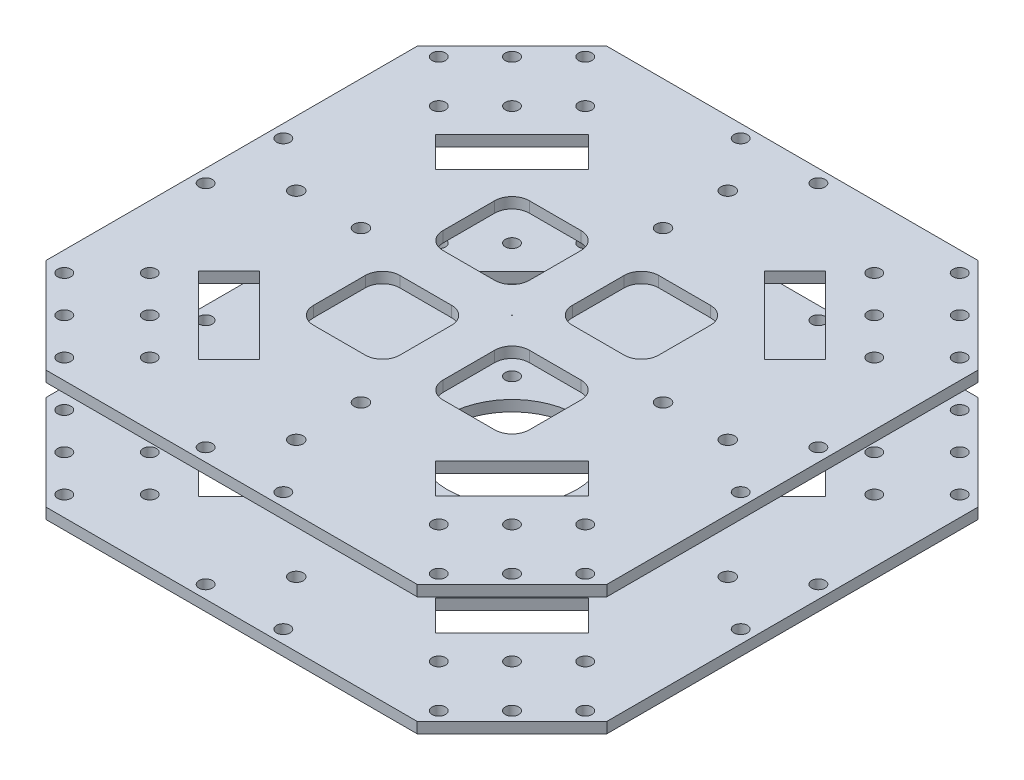
SolidWorks part; units mm, degrees
ref_plane "前视基准面" through (0, 0, 0) normal (0, 0, 1) x (1, 0, 0)
ref_plane "上视基准面" through (0, 0, 0) normal (0, 1, 0) x (1, 0, 0)
ref_plane "右视基准面" through (0, 0, 0) normal (1, 0, 0) x (0, 0, -1)
sketch "草图1" plane through (0, 0, 0) normal (0, 1, 0) x (1, 0, 0)
  line L1 (65, -65) -> (-65, -65)
  line L2 (65, -65) -> (65, 65)
  line L3 (65, 65) -> (-65, 65)
  line L4 (-65, -65) -> (-65, 65)
  line L5 (65, -65) -> (-65, 65) construction
  line L6 (65, 65) -> (-65, -65) construction
  point P0 (0, 0)
  dimension "D1" = 130
  dimension "D2" = 130
extrude "凸台-拉伸1" add sketch "草图1" along normal blind 2.5
ref_plane "基准面4" through (0, 27.5, 0) normal (0, 1, 0) x (1, 0, 0)
sketch "草图2" plane through (0, 27.5, 0) normal (0, 1, 0) x (1, 0, 0)
  line L1 (65, -65) -> (-65, -65)
  line L2 (65, -65) -> (65, 65)
  line L3 (65, 65) -> (-65, 65)
  line L4 (-65, -65) -> (-65, 65)
  line L5 (65, -65) -> (-65, 65) construction
  line L6 (65, 65) -> (-65, -65) construction
  point P0 (0, 0)
  dimension "D1" = 130
  dimension "D2" = 130
extrude "凸台-拉伸2" add sketch "草图2" along normal blind 2.5 separate body
sketch "草图3" plane through (0, 0, 0) normal (0, 1, 0) x (1, 0, 0)
  line L0 (0, 34.0658) -> (0, 0) construction
  line L1 (0, 0) -> (52.3615, 0) construction
  line L2 (-43, 65) -> (-65, 43)
  line L3 (65, 65) -> (-65, 65) construction
  line L4 (-65, 65) -> (-65, -65) construction
  line L5 (-65, 43) -> (-65, 65)
  line L6 (-65, 65) -> (-43, 65)
  line L7 (65, 65) -> (43, 65)
  line L8 (65, 43) -> (65, 65)
  line L9 (43, 65) -> (65, 43)
  line L10 (43, -65) -> (65, -43)
  line L11 (65, -43) -> (65, -65)
  line L12 (65, -65) -> (43, -65)
  line L13 (-65, -65) -> (-43, -65)
  line L14 (-65, -43) -> (-65, -65)
  line L15 (-43, -65) -> (-65, -43)
  dimension "D1" = 22
extrude "切除-拉伸1" cut sketch "草图3" against normal mid plane 500
sketch "草图5" plane through (0, 30, 0) normal (0, 1, 0) x (1, 0, 0)
  line L0 (0, 0) -> (-54, 54) construction
  line L1 (-65, 43) -> (-43, 65) construction
  line L2 (0, 0) -> (0, 31.4738) construction
  line L3 (0, 0) -> (-32.2224, 0) construction
  line L4 (-38.7284, 55.1295) -> (-46.9289, 46.9289) construction
  line L5 (-43.3934, 60.364) -> (-60.364, 43.3934) construction
  circle A2 centre (-60.364, 43.3934) radius 1.55
  circle A3 centre (-43.3934, 60.364) radius 1.55
  circle A4 centre (43.3934, 60.364) radius 1.55
  circle A5 centre (60.364, 43.3934) radius 1.55
  circle A6 centre (60.364, -43.3934) radius 1.55
  circle A7 centre (43.3934, -60.364) radius 1.55
  circle A8 centre (-43.3934, -60.364) radius 1.55
  circle A9 centre (-60.364, -43.3934) radius 1.55
  circle A10 centre (-50.4645, 33.4939) radius 1.55
  circle A11 centre (-33.4939, 50.4645) radius 1.55
  circle A12 centre (33.4939, 50.4645) radius 1.55
  circle A13 centre (50.4645, 33.4939) radius 1.55
  circle A14 centre (33.4939, -50.4645) radius 1.55
  circle A15 centre (50.4645, -33.4939) radius 1.55
  circle A16 centre (-33.4939, -50.4645) radius 1.55
  circle A17 centre (-50.4645, -33.4939) radius 1.55
  circle A18 centre (-51.8787, 51.8787) radius 1.55
  circle A19 centre (-41.9792, 41.9792) radius 1.55
  circle A20 centre (41.9792, 41.9792) radius 1.55
  circle A21 centre (51.8787, 51.8787) radius 1.55
  circle A22 centre (51.8787, -51.8787) radius 1.55
  circle A23 centre (41.9792, -41.9792) radius 1.55
  circle A24 centre (-41.9792, -41.9792) radius 1.55
  circle A25 centre (-51.8787, -51.8787) radius 1.55
  dimension "D1" = 3.1
  dimension "D2" = 3
  dimension "D3" = 24
  dimension "D4" = 7
extrude "切除-拉伸3" cut sketch "草图5" against normal mid plane 500
sketch "草图6" plane through (0, 30, 0) normal (0, 1, 0) x (1, 0, 0)
  circle A0 centre (0, 0) radius 0.05
  dimension "D1" = 0.1
extrude "切除-拉伸4" cut sketch "草图6" against normal blind 10
sketch "草图7" plane through (0, 30, 0) normal (0, 1, 0) x (1, 0, 0)
  line L0 (0, 0) -> (-65, 0) construction
  line L1 (-65, 43) -> (-65, -43) construction
  line L2 (-62, 0) -> (-62, 9) construction
  line L3 (0, 18.3729) -> (0, 0) construction
  line L4 (0, 0) -> (-41.9792, 41.9792) construction
  line L5 (62, 0) -> (62, 9) construction
  line L6 (0, -62) -> (-9, -62) construction
  line L7 (0, 62) -> (-9, 62) construction
  circle A0 centre (-62, 9) radius 1.55
  circle A1 centre (-62, -9) radius 1.55
  circle A2 centre (62, -9) radius 1.55
  circle A3 centre (62, 9) radius 1.55
  circle A4 centre (-9, -62) radius 1.55
  circle A5 centre (9, -62) radius 1.55
  circle A6 centre (9, 62) radius 1.55
  circle A7 centre (-9, 62) radius 1.55
  dimension "D1" = 3.1
  dimension "D2" = 3
  dimension "D3" = 18
extrude "切除-拉伸5" cut sketch "草图7" against normal blind 50
sketch "草图8" plane through (0, 30, 0) normal (0, 1, 0) x (1, 0, 0)
  line L0 (0, 25) -> (0, -25) construction
  line L1 (25, -25) -> (-25, -25)
  line L2 (25, -25) -> (25, 25)
  line L3 (25, 25) -> (-25, 25)
  line L4 (-25, -25) -> (-25, 25)
  line L5 (25, -25) -> (-25, 25) construction
  line L6 (25, 25) -> (-25, -25) construction
  line L7 (-25, 0) -> (25, 0) construction
  line L8 (-5, 25) -> (-5, 5)
  line L9 (5, 25) -> (5, 5)
  line L10 (-25, -5) -> (-5, -5)
  line L11 (-25, 5) -> (-5, 5)
  line L12 (5, 5) -> (25, 5)
  line L13 (-5, -5) -> (-5, -25)
  line L14 (5, -5) -> (25, -5)
  line L15 (5, -5) -> (5, -25)
  point P0 (0, 0)
  dimension "D1" = 50
  dimension "D2" = 50
  dimension "D3" = 10
extrude "切除-拉伸6" cut sketch "草图8" against normal blind 10 contours L4 L11 L8 L3 | L9 L12 L2 L3 | L14 L15 L1 L2 | L13 L10 L4 L1 region at (15, 30, 15) region at (-15, 30, 15) region at (15, 30, -15) region at (-15, 30, -15)
fillet "圆角1" radius 4 16 edges at (-25, 28.75, 25) (25, 28.75, 25) (25, 28.75, -25) (-25, 28.75, -25) (25, 28.75, 5) (5, 28.75, 25) (5, 28.75, 5) (-5, 28.75, 25) (-25, 28.75, 5) (-5, 28.75, 5) (25, 28.75, -5) (5, 28.75, -5) (-5, 28.75, -5) (-25, 28.75, -5) (5, 28.75, -25) (-5, 28.75, -25)
sketch "草图9" plane through (0, 0, 0) normal (0, -1, 0) x (1, 0, 0)
  line L1 (26, -22.65) -> (-26, -22.65) construction
  line L2 (26, -22.65) -> (26, 22.65) construction
  line L3 (26, 22.65) -> (-26, 22.65) construction
  line L4 (-26, -22.65) -> (-26, 22.65) construction
  line L5 (26, -22.65) -> (-26, 22.65) construction
  line L6 (26, 22.65) -> (-26, -22.65) construction
  line L7 (15.25, -15.25) -> (-15.25, -15.25) construction
  line L8 (15.25, -15.25) -> (15.25, 15.25) construction
  line L9 (15.25, 15.25) -> (-15.25, 15.25) construction
  line L10 (-15.25, -15.25) -> (-15.25, 15.25) construction
  line L11 (15.25, -15.25) -> (-15.25, 15.25) construction
  line L12 (15.25, 15.25) -> (-15.25, -15.25) construction
  circle A0 centre (-26, 22.65) radius 1.55
  circle A1 centre (26, 22.65) radius 1.55
  circle A2 centre (26, -22.65) radius 1.55
  circle A3 centre (-26, -22.65) radius 1.55
  circle A4 centre (-15.25, 15.25) radius 1.55
  circle A5 centre (15.25, 15.25) radius 1.55
  circle A6 centre (-15.25, -15.25) radius 1.55
  circle A7 centre (15.25, -15.25) radius 1.55
  point P0 (0, 0)
  point P10 (0, 0)
  dimension "D3" = 3.1
  dimension "D6" = 3.1
  dimension "D1" = 52
  dimension "D2" = 45.3
  dimension "D4" = 30.5
  dimension "D5" = 30.5
extrude "切除-拉伸7" cut sketch "草图9" against normal blind 10
sketch "草图11" plane through (0, 0, 0) normal (0, -1, 0) x (1, 0, 0)
  line L0 (0, 0) -> (0, 34.9488) construction
  line L1 (0, 0) -> (42.3942, 0) construction
  line L2 (-45.1612, 27.4835) -> (-27.4835, 45.1612)
  line L3 (-27.4835, 45.1612) -> (-20.4124, 38.0901)
  line L4 (-20.4124, 38.0901) -> (-38.0901, 20.4124)
  line L5 (-38.0901, 20.4124) -> (-45.1612, 27.4835)
  line L6 (-43, 65) -> (-65, 43) construction
  line L7 (-54, 54) -> (-36.3223, 36.3223) construction
  line L8 (54, 54) -> (36.3223, 36.3223) construction
  line L9 (38.0901, 20.4124) -> (45.1612, 27.4835)
  line L10 (20.4124, 38.0901) -> (38.0901, 20.4124)
  line L11 (27.4835, 45.1612) -> (20.4124, 38.0901)
  line L12 (45.1612, 27.4835) -> (27.4835, 45.1612)
  line L13 (54, -54) -> (36.3223, -36.3223) construction
  line L14 (-54, -54) -> (-36.3223, -36.3223) construction
  line L15 (45.1612, -27.4835) -> (27.4835, -45.1612)
  line L16 (27.4835, -45.1612) -> (20.4124, -38.0901)
  line L17 (20.4124, -38.0901) -> (38.0901, -20.4124)
  line L18 (38.0901, -20.4124) -> (45.1612, -27.4835)
  line L19 (-38.0901, -20.4124) -> (-45.1612, -27.4835)
  line L20 (-20.4124, -38.0901) -> (-38.0901, -20.4124)
  line L21 (-27.4835, -45.1612) -> (-20.4124, -38.0901)
  line L22 (-45.1612, -27.4835) -> (-27.4835, -45.1612)
  line L23 (0, 0) -> (54, 54) construction
  circle A0 centre (0, 0) radius 15
  dimension "D1" = 30
  dimension "D2" = 10
  dimension "D3" = 25
  dimension "D4" = 25
extrude "切除-拉伸8" cut sketch "草图11" against normal blind 10 contours A0 region at (0, 0, 0)
extrude "切除-拉伸9" cut sketch "草图11<3>" against normal blind 40 contours L18 L17 L16 L15 | L19 L22 L21 L20 | L5 L4 L3 L2 | L9 L12 L11 L10 region at (-32.7868, 0, 32.7868) region at (32.7868, 0, 32.7868) region at (32.7868, 0, -32.7868) region at (-32.7868, 0, -32.7868)
sketch "草图11<3>" plane through (0, 0, 0) normal (0, -1, 0) x (1, 0, 0) same geometry as "草图11"
sketch "草图12" plane through (0, 0, 0) normal (0, -1, 0) x (1, 0, 0)
  line L0 (0, 47.2393) -> (0, 0) construction
  line L1 (0, 0) -> (41.9792, 41.9792) construction
  line L2 (0, 0) -> (45.5522, 0) construction
  line L3 (47.2393, 0) -> (0, 0) construction
  circle A0 centre (0, 50) radius 1.6
  circle A1 centre (0, 35) radius 1.6
  circle A2 centre (0, -35) radius 1.6
  circle A3 centre (0, -50) radius 1.6
  circle A4 centre (-50, 0) radius 1.6
  circle A5 centre (-35, 0) radius 1.6
  circle A6 centre (35, 0) radius 1.6
  circle A7 centre (50, 0) radius 1.6
  dimension "D1" = 3.2
  dimension "D2" = 50
  dimension "D3" = 15
extrude "切除-拉伸10" cut sketch "草图12" against normal blind 50
